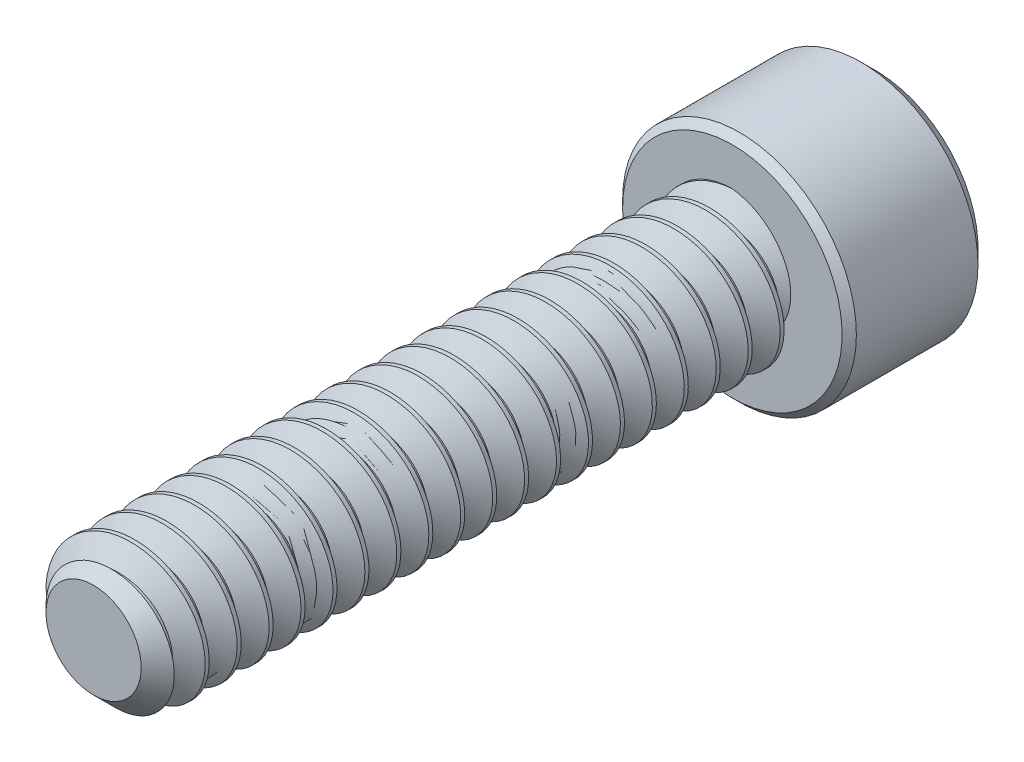
SolidWorks part; units mm, degrees
ref_plane "Front Plane" through (0, 0, 0) normal (0, 0, 1) x (1, 0, 0)
ref_plane "Top Plane" through (0, 0, 0) normal (0, 1, 0) x (1, 0, 0)
ref_plane "Right Plane" through (0, 0, 0) normal (1, 0, 0) x (0, 0, -1)
sketch "Sketch1" plane through (0, 0, 0) normal (0, 0, 1) x (1, 0, 0)
  line L0 (0, 1.4224) -> (0, -1.4224) construction
  circle A0 centre (0, 0) radius 1.4224
  dimension "OD" = 2.8448
extrude "Extrude1" add sketch "Sketch1" against normal blind 12.7
sketch "Sketch2" plane through (0, 0, 0) normal (0, 0, 1) x (1, 0, 0)
  circle A0 centre (0, 0) radius 1.4224 construction
  circle A1 centre (0, 0) radius 1.4224
curve "Helix/Spiral1" pitch 0.635 height 13.335 radius 1.4224 centre (0, 0, 0) axis (0, 0, -1) start towards (0, 1, 0) parameters "pitch"=0.635
chamfer "Chamfer3" distance 0.4763 angle 45 1 edges at (1.4224, 0, 0)
sketch "Sketch3" plane through (0, 0, 0) normal (1, 0, 0) x (0, 0, -1)
  line L0 (-0.5556, 1.4224) -> (-0.3175, 1.01)
  line L1 (-0.3175, 1.01) -> (-0.2381, 1.01)
  line L2 (-0.2381, 1.01) -> (0, 1.4224)
  line L3 (-0.5556, 1.4224) -> (0, 1.4224)
  line L4 (-0.2778, 1.4224) -> (-0.2778, 1.01) construction
  line L5 (-0.4366, 1.2162) -> (-0.1191, 1.2162) construction
  line L6 (0, 1.4224) -> (0, -1.4224) construction
  dimension "D1" = 0.0794
  dimension "D2" = 0.3175
  dimension "D3" = 60
sweep "Cut-Sweep1" cut profiles "Sketch3" path "Helix/Spiral1" align with end faces yes
sketch "Sketch6" plane through (0, 0, -12.7) normal (0, 0, -1) x (-1, 0, 0)
  circle A0 centre (0, 0) radius 2.3241
  dimension "head dia" = 4.6482
extrude "Extrude2" add sketch "Sketch6" along normal blind 2.8448
sketch "Sketch7" plane through (0, 0, -15.5448) normal (0, 0, -1) x (-1, 0, 0)
  line L1 (0, 1.3748) -> (-1.1906, 0.6874)
  line L2 (-1.1906, 0.6874) -> (-1.1906, -0.6874)
  line L3 (-1.1906, -0.6874) -> (0, -1.3748)
  line L4 (0, -1.3748) -> (1.1906, -0.6874)
  line L5 (1.1906, -0.6874) -> (1.1906, 0.6874)
  line L6 (1.1906, 0.6874) -> (0, 1.3748)
  circle A0 centre (0, 0) radius 1.1906 construction
  dimension "hex dia" = 2.3813
extrude "Cut-Extrude1" cut sketch "Sketch7" against normal blind 1.7859
sketch "Sketch8" plane through (0, 0, -15.5448) normal (0, 0, -1) x (-1, 0, 0)
  circle A0 centre (0, 0) radius 1.3748
extrude "Cut-Extrude2" cut sketch "Sketch8" against normal blind 0.2845 draft 45
chamfer "Chamfer1" distance 0.2845 angle 45 1 edges at (-2.3241, 0, -15.5448)
chamfer "Chamfer2" distance 0.1422 angle 45 1 edges at (-2.3241, 0, -12.7)
sketch "Sketch9" plane through (0, 0, 0) normal (1, 0, 0) x (0, 0, -1)
  line L0 (0, 1.4224) -> (0, -1.4224) construction
  line L1 (3.4925, 1.4224) -> (3.4925, -1.4224) construction
  line L2 (12.7, 2.3241) -> (12.7, -2.3241) construction
  line L3 (15.5448, 2.3241) -> (15.5448, -2.3241) construction
  line L4 (15.5448, 0) -> (0, 0) construction
  dimension "D1" = 3.4925
  dimension "D2" = 2.8448
  dimension "D3" = 4.6482
  dimension "D4" = 12.7
equation "\"D3@Helix/Spiral1\" = \"screw length@Extrude1\"+\"pitch@Helix/Spiral1\""
equation "\"D1@Sketch3\" = \"pitch@Helix/Spiral1\"*.125"
equation "\"D2@Sketch3\" = \"pitch@Helix/Spiral1\"*.5"
equation "\"D1@Cut-Extrude1\" = \"hex dia@Sketch7\"*.75"
equation "\"D1@Chamfer1\" = \"head depth@Extrude2\"/10"
equation "\"D1@Sketch9\" = \"pitch@Helix/Spiral1\"*5.5"
equation "\"D1@Chamfer2\" = \"D1@Chamfer1\"/2"
equation "\"D1@Cut-Extrude2\" = \"D1@Chamfer2\"*2"
equation "\"D1@Chamfer3\" = \"pitch@Helix/Spiral1\"*.750"
equation "\"D2@Sketch9\" = \"head depth@Extrude2\""
equation "\"D3@Sketch9\" = \"head dia@Sketch6\""
equation "\"D4@Sketch9\" = \"screw length@Extrude1\""
